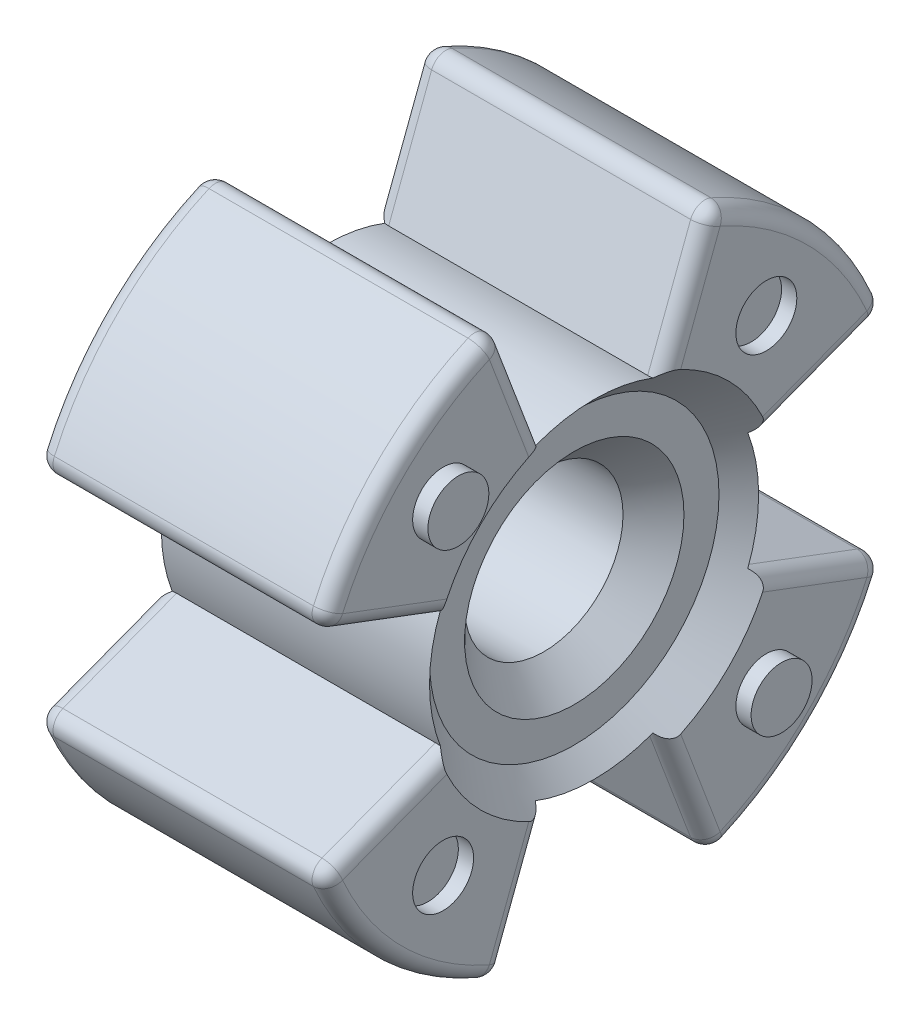
SolidWorks part; units mm, degrees
ref_plane "Front" through (0, 0, 0) normal (0, 0, 1) x (1, 0, 0)
ref_plane "Top" through (0, 0, 0) normal (0, 1, 0) x (1, 0, 0)
ref_plane "Right" through (0, 0, 0) normal (1, 0, 0) x (0, 0, -1)
sketch "Эскиз1" plane through (0, 0, 0) normal (1, 0, 0) x (0, 0, -1)
  line L0 (1.9091, 5.0513) -> (3.5, 9.2607)
  line L1 (0, 9.542) -> (0, 0) construction
  line L2 (-1.9091, 5.0513) -> (-3.5, 9.2607)
  line L3 (0, 0) -> (10.6021, 0) construction
  line L4 (-1.9091, -5.0513) -> (-3.5, -9.2607)
  line L5 (1.9091, -5.0513) -> (3.5, -9.2607)
  line L6 (5.0513, -1.9091) -> (9.2607, -3.5)
  line L7 (5.0513, 1.9091) -> (9.2607, 3.5)
  line L8 (-5.0513, -1.9091) -> (-9.2607, -3.5)
  line L9 (-5.0513, 1.9091) -> (-9.2607, 3.5)
  line L10 (0, 0) -> (1.9091, -5.0513) construction
  line L11 (0, 0) -> (-5.0513, -1.9091) construction
  arc A0 (-9.2607, -3.5) -> (-3.5, -9.2607) centre (0, 0) ccw
  arc A1 (-5.0513, 1.9091) -> (-5.0513, -1.9091) centre (0, 0) ccw
  arc A2 (9.2607, 3.5) -> (3.5, 9.2607) centre (0, 0) ccw
  arc A3 (3.5, -9.2607) -> (9.2607, -3.5) centre (0, 0) ccw
  arc A4 (-3.5, 9.2607) -> (-9.2607, 3.5) centre (0, 0) ccw
  arc A6 (1.9091, 5.0513) -> (-1.9091, 5.0513) centre (0, 0) ccw
  arc A7 (5.0513, -1.9091) -> (5.0513, 1.9091) centre (0, 0) ccw
  arc A8 (-1.9091, -5.0513) -> (1.9091, -5.0513) centre (0, 0) ccw
  dimension "D4" = 2
  dimension "D3" = 7
  dimension "D5" = 90
extrude "Бобышка-Вытянуть1" add sketch "Эскиз1" along normal mid plane 9.5 contours L9 A4 L2 A6 L0 A2 L7 A7 L6 A3 L5 A8 L4 A0 L8 A1
fillet "Скругление3" radius 0.5 8 edges at (0, -3.5, -9.2607) (0, -9.2607, -3.5) (0, -9.2607, 3.5) (0, -3.5, 9.2607) (0, 9.2607, -3.5) (0, 9.2607, 3.5) (0, 3.5, 9.2607) (0, 3.5, -9.2607)
fillet "Скругление2" radius 0.5 40 edges at (-4.75, 2.6138, -6.9159) (-4.75, -6.9159, -2.6138) (-4.75, -2.6138, 6.9159) (-4.75, 6.9159, -2.6138) (4.75, 2.6138, -6.9159) (4.75, -6.9159, -2.6138) (4.75, -2.6138, 6.9159) (4.75, 6.9159, -2.6138) (-4.75, -2.6138, -6.9159) (-4.75, -6.9159, 2.6138) (-4.75, 2.6138, 6.9159) (-4.75, 6.9159, 2.6138) (4.75, -2.6138, -6.9159) (4.75, -6.9159, 2.6138) (4.75, 2.6138, 6.9159) (4.75, 6.9159, 2.6138) (-4.75, -9.0648, -3.5927) (-4.75, -7.0004, -7.0004) (-4.75, -3.5927, -9.0648) (-4.75, -3.5927, 9.0648) (-4.75, -7.0004, 7.0004) (-4.75, -9.0648, 3.5927) (-4.75, 3.5927, 9.0648) (-4.75, 7.0004, 7.0004) (-4.75, 9.0648, 3.5927) (4.75, -9.0648, -3.5927) (4.75, -7.0004, -7.0004) (4.75, -3.5927, -9.0648) (4.75, -3.5927, 9.0648) (4.75, -7.0004, 7.0004) (4.75, -9.0648, 3.5927) (4.75, 3.5927, 9.0648) (4.75, 7.0004, 7.0004) (4.75, 9.0648, 3.5927) (-4.75, 9.0648, -3.5927) (4.75, 9.0648, -3.5927) (-4.75, 7.0004, -7.0004) (4.75, 7.0004, -7.0004) (-4.75, 3.5927, -9.0648) (4.75, 3.5927, -9.0648)
sketch "Эскиз2" plane through (4.75, 0, 0) normal (1, 0, 0) x (0, 0, -1)
  circle A0 centre (0, 0) radius 2.6
  dimension "D1" = 5.2
extrude "Вырез-Вытянуть1" cut sketch "Эскиз2" against normal through all
sketch "Эскиз3" plane through (4.75, 0, 0) normal (1, 0, 0) x (0, 0, -1)
  circle A1 centre (0, 0) radius 4.75
  dimension "D1" = 9.5
extrude "Вырез-Вытянуть2" cut sketch "Эскиз3" against normal blind 1
chamfer "Фаска1" distance 1 angle 45 1 edges at (4.75, 0, -4.75)
mirror "Зеркальное отражение7" about plane through (0, 0, 0) normal (1, 0, 0) of "Вырез-Вытянуть2"
chamfer "Фаска2" distance 1 angle 45 1 edges at (-4.75, 0, -4.75)
chamfer "Фаска3" distance 1 angle 45 2 edges at (-3.75, 0, 2.6) (3.75, 0, -2.6)
sketch "Эскиз4" plane through (4.75, 0, 0) normal (1, 0, 0) x (0, 0, -1)
  line L0 (0, 0) -> (-6.6468, 6.6468) construction
  circle A0 centre (0, 0) radius 7.5 construction
  arc A1 (-3.7862, 8.6037) -> (-8.6037, 3.7862) centre (0, 0) ccw construction
  circle A2 centre (-5.3033, 5.3033) radius 1
  circle A3 centre (5.3033, -5.3033) radius 1
  point P12 (0, 0)
  dimension "D1" = 15
  dimension "D2" = 2
  dimension "D3" = 2
extrude "Бобышка-Вытянуть2" add sketch "Эскиз4" along normal blind 0.5
sketch "Эскиз5" plane through (4.75, 0, 0) normal (1, 0, 0) x (0, 0, -1)
  circle A4 centre (-5.3033, -5.3033) radius 1
  circle A5 centre (5.3033, 5.3033) radius 1
  point P12 (0, 0)
extrude "Вырез-Вытянуть3" cut sketch "Эскиз5" against normal blind 0.5
sketch "Эскиз7" plane through (-4.75, 0, 0) normal (-1, 0, 0) x (0, 0, 1)
  circle A0 centre (5.3033, -5.3033) radius 1 construction
  circle A1 centre (-5.3033, 5.3033) radius 1 construction
  circle A2 centre (5.3033, -5.3033) radius 1
  circle A3 centre (-5.3033, 5.3033) radius 1
extrude "Бобышка-Вытянуть3" add sketch "Эскиз7" along normal blind 0.5
